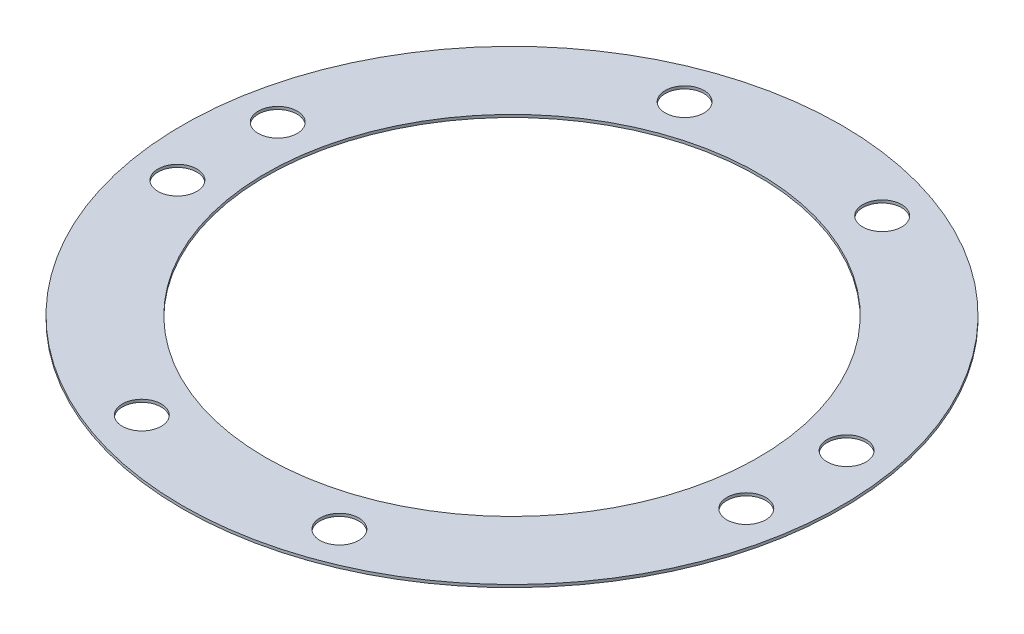
SolidWorks part; units mm, degrees
ref_plane "Front Plane" through (0, 0, 0) normal (0, 0, 1) x (1, 0, 0)
ref_plane "Top Plane" through (0, 0, 0) normal (0, 1, 0) x (1, 0, 0)
ref_plane "Right Plane" through (0, 0, 0) normal (1, 0, 0) x (0, 0, -1)
sketch "Sketch1" plane through (0, 0, 0) normal (0, 1, 0) x (1, 0, 0)
  line L0 (0, 106.2698) -> (0, -119.5036) construction
  line L1 (137.4689, 0) -> (-189.0602, 0) construction
  line L2 (0, 0) -> (41.6582, 114.455) construction
  line L3 (0, 0) -> (-43.0168, 118.1877) construction
  line L4 (0, 0) -> (-76.815, 13.5446) construction
  line L5 (0, 0) -> (-76.815, -13.5446) construction
  circle A0 centre (0, 0) radius 66.5
  circle A1 centre (0, 0) radius 89
  circle A6 centre (26.6776, 73.296) radius 5.25
  circle A7 centre (-26.6776, 73.296) radius 5.25
  circle A8 centre (-76.815, 13.5446) radius 5.25
  circle A9 centre (-76.815, -13.5446) radius 5.25
  circle A10 centre (-26.6776, -73.296) radius 5.25
  circle A11 centre (26.6776, -73.296) radius 5.25
  circle A13 centre (76.815, 13.5446) radius 5.25
  circle A14 centre (76.815, -13.5446) radius 5.25
  dimension "D1" = 178
  dimension "D2" = 133
  dimension "D4" = 10.5
  dimension "D7" = 10.5
  dimension "D10" = 10.5
  dimension "D11" = 10.5
  dimension "D12" = 10.5
  dimension "D13" = 10.5
  dimension "D14" = 10.5
  dimension "D15" = 10.5
  dimension "D5" = 20
  dimension "D6" = 20
  dimension "D8" = 10
  dimension "D9" = 10
base flange "Base-Flange1" sketch "Sketch1" thickness 0.7366 reverse thickness direction no parameters "D1"=0.7366
sketch "Sketch7" plane through (0, 0, 0) normal (0, 1, 0) x (1, 0, 0)
  line L0 (-37.5, 80.714) -> (37.5, 80.714)
  line L1 (-37.5, -80.714) -> (37.5, -80.714)
  line L2 (-85.9095, 23.25) -> (-85.9095, -23.25)
  line L3 (85.9095, 23.25) -> (85.9095, -23.25)
  circle A0 centre (0, 0) radius 89 construction
  circle A1 centre (0, 0) radius 89 construction
  dimension "D1" = 75
  dimension "D2" = 75
  dimension "D3" = 46.5
  dimension "D4" = 46.5
sketch "Bend-Lines1" [suppressed] plane through (0, 0, 0) normal (0, 1, 0) x (1, 0, 0)
sketch "Bounding-Box1" [suppressed] plane through (0, 0, 0) normal (0, 1, 0) x (1, 0, 0)
sheet metal parameters "Sheet-Metal1" thickness 0.7366 parameters "D1"=0.7366
flat pattern "Flat-Pattern1" [suppressed]
sketch "Bend-Lines2" plane through (0, 0, 0) normal (0, 1, 0) x (1, 0, 0)
sketch3d "Bounding-Box2" [suppressed]
  line L0 (89.0233, -88.9766, 0) -> (-88.9766, -89.0233, 0) construction
  line L1 (88.9766, 89.0233, 0) -> (-89.0233, 88.9766, 0) construction
  line L2 (89.0233, -88.9766, 0) -> (88.9766, 89.0233, 0) construction
  line L3 (-88.9766, -89.0233, 0) -> (-89.0233, 88.9766, 0) construction
